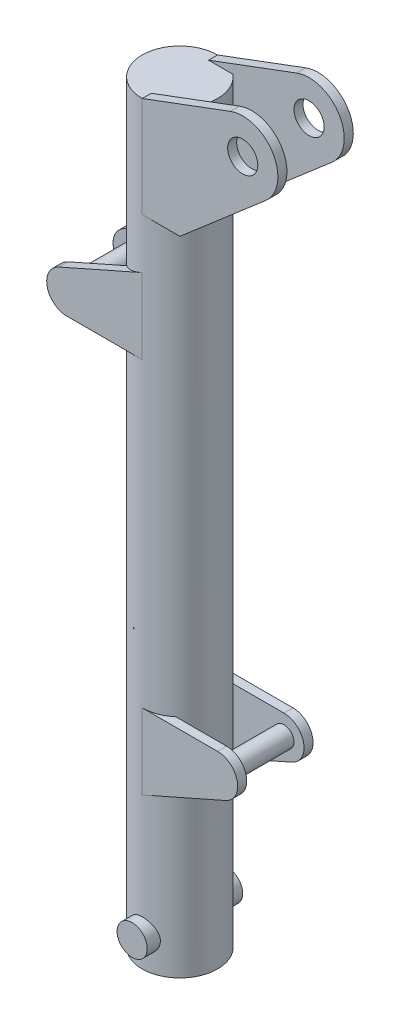
SolidWorks part; units mm, degrees
material "AISI 4340 Steel, normalized"
ref_plane "Front Plane" through (0, 0, 0) normal (0, 0, 1) x (1, 0, 0)
ref_plane "Top Plane" through (0, 0, 0) normal (0, 1, 0) x (1, 0, 0)
ref_plane "Right Plane" through (0, 0, 0) normal (1, 0, 0) x (0, 0, -1)
sketch "Sketch2" plane through (0, 0, 0) normal (0, 1, 0) x (1, 0, 0)
  circle A0 centre (0, 0) radius 75
  dimension "D1" = 150
extrude "Boss-Extrude1" add sketch "Sketch2" along normal blind 1500
shell "Shell4" thickness 10
ref_plane "Plane2" through (0, 0, 75) normal (0, 0, 1) x (1, 0, 0)
sketch "Sketch3" plane through (0, 0, 0) normal (0, 0, 1) x (1, 0, 0)
  line L0 (0, 450) -> (150, 450)
  line L2 (0, 300) -> (0, 450)
  line L3 (0, 300) -> (166.1647, 373.4117)
  line L4 (0, 1200) -> (0, 1050)
  line L5 (0, 1050) -> (-150, 1050)
  line L6 (0, 1200) -> (-166.1647, 1126.5883)
  line L7 (75, 1500) -> (-75, 1500) construction
  line L17 (0, 1300) -> (0, 1500)
  line L18 (0, 1500) -> (175.5, 1565.5725)
  line L20 (245.6739, 1446.9538) -> (75, 1300)
  line L21 (75, 0) -> (75, 1500) construction
  line L22 (75, 1300) -> (0, 1300)
  line L23 (0, 1500) -> (200, 1500) construction
  arc A0 (166.1647, 373.4117) -> (150, 450) centre (150, 410) ccw
  circle A1 centre (150, 410) radius 20 construction
  arc A2 (-166.1647, 1126.5883) -> (-150, 1050) centre (-150, 1090) ccw
  circle A3 centre (-150, 1090) radius 20 construction
  circle A7 centre (200, 1500) radius 30
  arc A8 (245.6739, 1446.9538) -> (175.5, 1565.5725) centre (200, 1500) ccw
  point P13 (253.6656, 1529.4149)
  point P14 (186.7703, 1571.4868)
  dimension "D1" = 40
  dimension "D2" = 20
  dimension "D3" = 150
  dimension "D6" = 20
  dimension "D7" = 40
  dimension "D11" = 60
  dimension "D12" = 40
  dimension "D4" = 300
  dimension "D5" = 150
  dimension "D8" = 300
  dimension "D9" = 150
  dimension "D10" = 150
  dimension "D13" = 200
  dimension "D14" = 200
extrude "Boss-Extrude2" add sketch "Sketch3" against normal blind 18 from surface starting at plane "Plane2"
sketch "Sketch10" plane through (0, 0, 0) normal (0, 0, 1) x (1, 0, 0)
  circle A0 centre (0, 60) radius 30
  dimension "D1" = 60
  dimension "D2" = 60
sketch "Sketch11" plane through (0, 0, 0) normal (0, -1, 0) x (1, 0, 0)
  line L0 (0, 0) -> (-75, 0) construction
  line L1 (-75, 0) -> (75, 0) construction
  circle A0 centre (0, 0) radius 75 construction
ref_plane "Plane4" through (0, 0, 0) normal (0, 0, -1) x (-1, 0, 0)
mirror "Mirror11" about plane through (0, 0, 0) normal (0, 0, -1) of "Boss-Extrude2"
extrude "Boss-Extrude3" add sketch "Sketch10" along normal mid plane 190
sketch "Sketch12" plane through (0, 0, 0) normal (0, 0, 1) x (1, 0, 0)
  circle A0 centre (150, 410) radius 20 construction
  circle A2 centre (-150, 1090) radius 20 construction
  circle A3 centre (150, 410) radius 20
  circle A5 centre (-150, 1090) radius 20
extrude "Boss-Extrude4" add sketch "Sketch12" along normal mid plane 150
